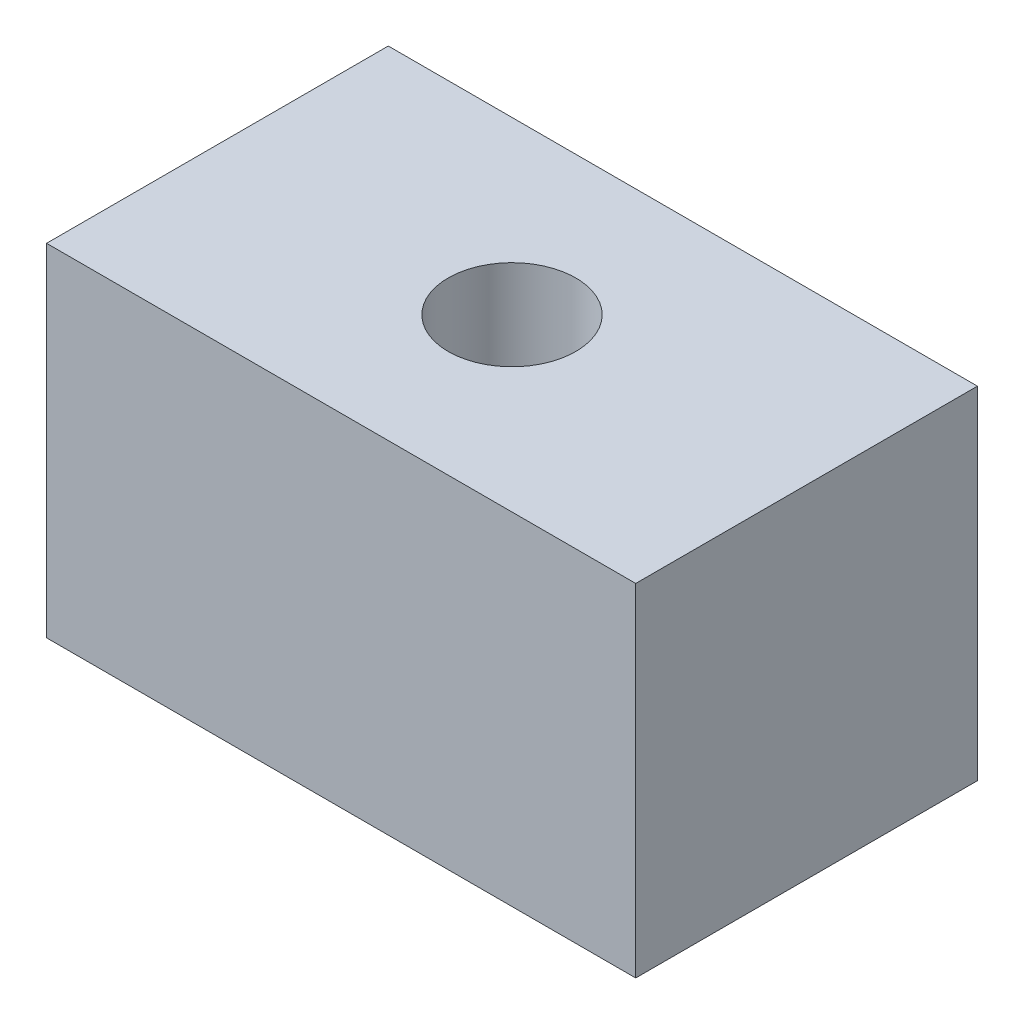
SolidWorks part; units mm, degrees
ref_plane "Front Plane" through (0, 0, 0) normal (0, 0, 1) x (1, 0, 0)
ref_plane "Top Plane" through (0, 0, 0) normal (0, 1, 0) x (1, 0, 0)
ref_plane "Right Plane" through (0, 0, 0) normal (1, 0, 0) x (0, 0, -1)
sketch "Sketch1" plane through (0, 0, 0) normal (1, 0, 0) x (0, 0, -1)
  line L1 (-7.366, 7.366) -> (7.366, 7.366)
  line L2 (-7.366, 7.366) -> (-7.366, -7.366)
  line L3 (-7.366, -7.366) -> (7.366, -7.366)
  line L4 (7.366, 7.366) -> (7.366, -7.366)
  line L5 (-7.366, 7.366) -> (7.366, -7.366) construction
  line L6 (-7.366, -7.366) -> (7.366, 7.366) construction
  point P0 (0, 0)
  dimension "D1" = 14.732
  dimension "D2" = 14.732
extrude "Boss-Extrude1" add sketch "Sketch1" along normal blind 25.4
sketch "Sketch2" plane through (0, 7.366, 0) normal (0, 1, 0) x (1, 0, 0)
  line L0 (0, 7.366) -> (0, -7.366) construction
  circle A0 centre (12.7, 0) radius 2.75
  point P6 (0, 0)
  dimension "D1" = 5.5
  dimension "D2" = 12.7
extrude "Cut-Extrude1" cut sketch "Sketch2" against normal through all
sketch "Sketch3" plane through (0, 0, -7.366) normal (0, 0, -1) x (-1, 0, 0)
  line L0 (0, -7.366) -> (0, 7.366) construction
  line L1 (0, 3.366) -> (-10, 3.366)
  line L2 (0, 3.366) -> (0, -3.492)
  line L3 (0, -3.492) -> (-10, -3.492)
  line L4 (-10, 3.366) -> (-10, -3.492)
  line L5 (-10, -0.063) -> (-4.92, -0.063) construction
  line L6 (-25.4, 7.366) -> (0, 7.366) construction
  circle A0 centre (-4.92, -0.063) radius 1.5875
  dimension "D2" = 3.175
  dimension "D1" = 6.858
  dimension "D3" = 5.08
  dimension "D4" = 10
  dimension "D5" = 4
extrude "Cut-Extrude2" cut sketch "Sketch3" against normal blind 1.778
fillet "Fillet1" radius 0.7937 2 edges at (10, 3.366, -6.477) (10, -3.492, -6.477)
sketch "Sketch5" plane through (0, 0, -7.366) normal (0, 0, -1) x (-1, 0, 0)
  line L0 (0, -7.366) -> (0, -3.492)
  line L1 (0, -7.366) -> (-3.9016, -7.366)
  line L2 (-25.4, -7.366) -> (0, -7.366) construction
